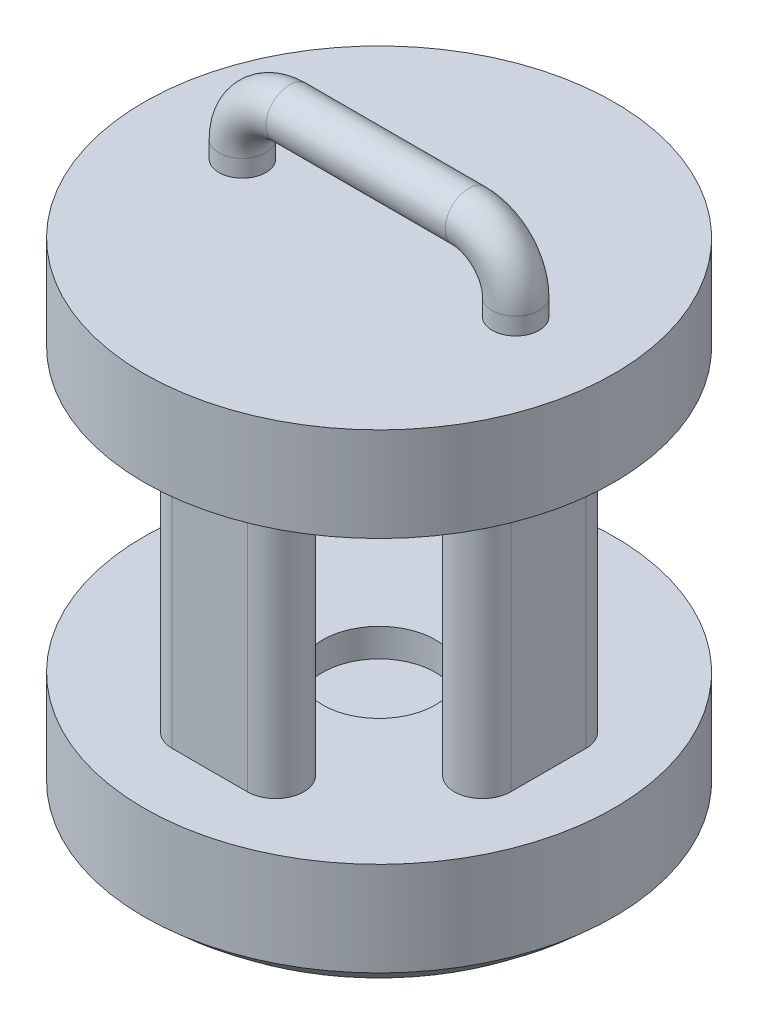
SolidWorks part; units mm, degrees
ref_plane "Front Plane" through (0, 0, 0) normal (0, 0, 1) x (1, 0, 0)
ref_plane "Top Plane" through (0, 0, 0) normal (0, 1, 0) x (1, 0, 0)
ref_plane "Right Plane" through (0, 0, 0) normal (1, 0, 0) x (0, 0, -1)
sketch "Sketch1" plane through (0, 0, 0) normal (0, 1, 0) x (1, 0, 0)
  circle A0 centre (0, 0) radius 6.35
  dimension "D1" = 12.7
extrude "button" add sketch "Sketch1" along normal blind 2.54
ref_axis "central axis" through (0, 2.54, 0) along (0, -1, 0)
sketch "Sketch2" plane through (0, 2.54, 0) normal (0, 1, 0) x (1, 0, 0)
  line L0 (-1.016, -3.81) -> (1.016, -3.81) construction
  line L1 (-1.016, -3.048) -> (1.016, -3.048)
  line L2 (-1.016, -4.572) -> (1.016, -4.572)
  arc A0 (-1.016, -3.048) -> (-1.016, -4.572) centre (-1.016, -3.81) ccw
  arc A1 (1.016, -4.572) -> (1.016, -3.048) centre (1.016, -3.81) ccw
  point P2 (0, -3.81)
  dimension "D2" = 0.762
  dimension "D1" = 2.032
  dimension "D3" = 0
  dimension "D4" = 3.81
extrude "one leg" add sketch "Sketch2" along normal blind 7.62
pattern_circular "moar legs" count 4 over 360 about axis through (0, 2.54, 0) along (0, -1, 0) of "one leg"
sketch "Sketch3" plane through (0, 10.16, 0) normal (0, 1, 0) x (1, 0, 0)
  circle A0 centre (0, 0) radius 6.35
extrude "button bottom" add sketch "Sketch3" along normal blind 2.54
dome "button top" faces to dome 1 distance 2.54 reverse direction no elliptical dome no face at (0, 0, 6.35) parameters "D1"=2.54
sketch "Sketch4" plane through (0, 0, 0) normal (0, 0, 1) x (1, 0, 0)
  line L1 (0, 11.43) -> (0, 15.4488) construction
  line L4 (-3.6897, 12.7) -> (-3.6897, 13.1638)
  line L5 (6.35, 12.7) -> (-6.35, 12.7) construction
  line L6 (-2.4197, 14.4338) -> (2.4197, 14.4338)
  line L7 (3.6897, 12.7) -> (3.6897, 13.1638)
  arc A0 (3.6897, 13.1638) -> (2.4197, 14.4338) centre (2.4197, 13.1638) ccw
  arc A1 (-3.6897, 13.1638) -> (-2.4197, 14.4338) centre (-2.4197, 13.1638) cw
  point P10 (0, 14.4338)
  point P12 (3.6897, 14.4338)
  point P15 (-3.6897, 14.4338)
  dimension "D1" = 1.27
sketch "Sketch5" plane through (0, 12.7, 0) normal (0, 1, 0) x (1, 0, 0)
  circle A0 centre (-3.6897, 0) radius 0.635
  dimension "D1" = 1.27
sweep "handle for linkage" add profiles "Sketch5" path "Sketch4"
sketch "Sketch6" plane through (0, 2.54, 0) normal (0, 1, 0) x (1, 0, 0)
  circle A0 centre (0, 0) radius 1.524
  dimension "D1" = 3.048
extrude "recess for spring" cut sketch "Sketch6" against normal blind 0.762
